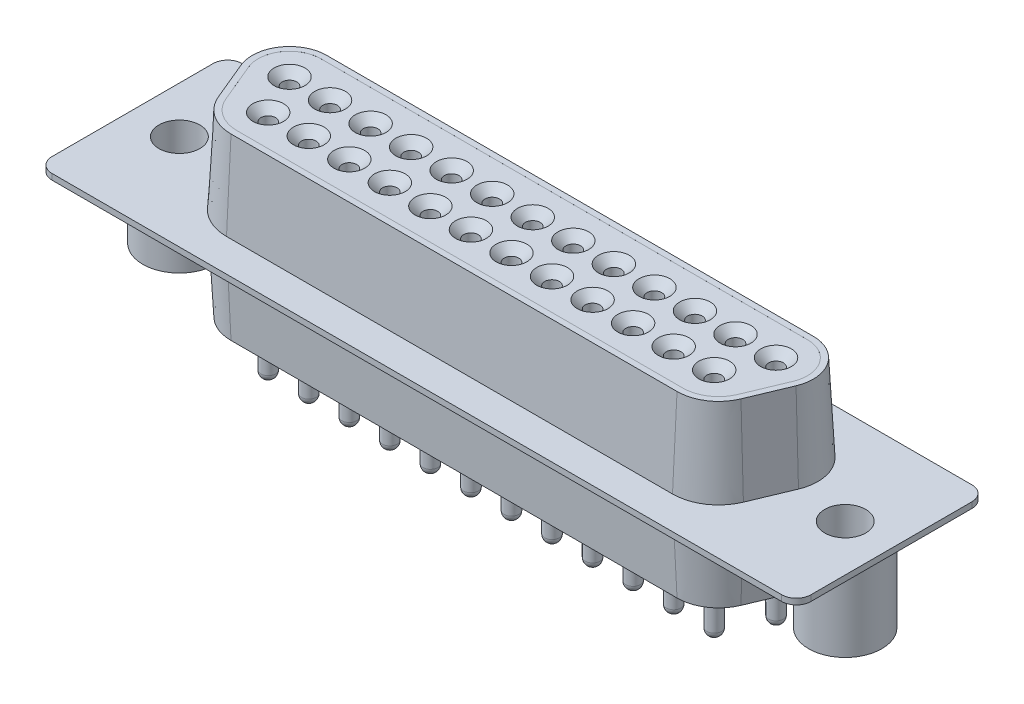
SolidWorks part; units mm, degrees
ref_plane "Front" through (0, 0, 0) normal (0, 0, 1) x (1, 0, 0)
ref_plane "Top" through (0, 0, 0) normal (0, 1, 0) x (1, 0, 0)
ref_plane "Right" through (0, 0, 0) normal (1, 0, 0) x (0, 0, -1)
sketch "Sketch1" plane through (0, 0, 0) normal (0, 1, 0) x (1, 0, 0)
  line L0 (0, 2.54) -> (33.24, 2.54)
  line L1 (1.385, -5.38) -> (31.855, -5.38)
  line L2 (34.476, -3.6337) -> (35.5841, -0.9782)
  line L3 (16.62, 2.54) -> (16.62, -5.38) construction
  line L4 (-1.236, -3.6337) -> (-2.3441, -0.9782)
  arc A0 (31.855, -5.38) -> (34.476, -3.6337) centre (31.855, -2.54) ccw
  arc A1 (35.5841, -0.9782) -> (33.24, 2.54) centre (33.24, 0) ccw
  arc A2 (-2.3441, -0.9782) -> (0, 2.54) centre (0, 0) cw
  arc A3 (1.385, -5.38) -> (-1.236, -3.6337) centre (1.385, -2.54) cw
  dimension "D3" = 2.84
  dimension "D6" = 2.54
  dimension "D1" = 33.24
  dimension "D2" = 30.47
  dimension "D4" = 2.54
  dimension "D5" = 7.92
extrude "Base-Extrude" add sketch "Sketch1" against normal blind 5.91 draft 3 draft outward yes
sketch "Sketch2" plane through (0, -5.91, 0) normal (0, -1, 0) x (1, 0, 0)
  line L0 (16.62, -2.8497) -> (16.62, -5.08) construction
  line L1 (41.545, 7.92) -> (-8.305, 7.92)
  line L2 (42.545, 6.92) -> (42.545, -4.08)
  line L3 (41.545, -5.08) -> (-8.305, -5.08)
  line L4 (-9.305, 6.92) -> (-9.305, -4.08)
  line L5 (33.24, -2.8497) -> (0, -2.8497) construction
  line L6 (16.62, -2.8497) -> (16.62, 5.6897) construction
  line L7 (1.385, 5.6897) -> (31.855, 5.6897) construction
  line L8 (16.62, 1.42) -> (42.545, 1.42) construction
  arc A0 (42.545, 6.92) -> (41.545, 7.92) centre (41.545, 6.92) ccw
  arc A1 (41.545, -5.08) -> (42.545, -4.08) centre (41.545, -4.08) ccw
  arc A2 (-9.305, 6.92) -> (-8.305, 7.92) centre (-8.305, 6.92) cw
  arc A3 (-9.305, -4.08) -> (-8.305, -5.08) centre (-8.305, -4.08) ccw
  point P15 (42.545, 7.92)
  point P18 (42.545, -5.08)
  point P23 (-9.305, -5.08)
  dimension "D3" = 1
  dimension "D1" = 51.85
  dimension "D2" = 13
extrude "Boss-Extrude1" add sketch "Sketch2" along normal blind 0.2
sketch "Sketch3" plane through (0, 0, 0) normal (0, 1, 0) x (-1, 0, 0)
  line L8 (-33.24, -2.14) -> (0, -2.14)
  line L9 (1.9749, 0.8241) -> (0.8668, 3.4797)
  line L10 (-1.385, 4.98) -> (-31.855, 4.98)
  line L11 (-34.1068, 3.4797) -> (-35.2149, 0.8241)
  line L12 (-33.24, -2.14) -> (0, -2.14)
  line L13 (1.9749, 0.8241) -> (0.8668, 3.4797)
  line L14 (-1.385, 4.98) -> (-31.855, 4.98)
  line L15 (-34.1068, 3.4797) -> (-35.2149, 0.8241)
  arc A8 (0, -2.14) -> (1.9749, 0.8241) centre (0, 0) ccw
  arc A9 (0.8668, 3.4797) -> (-1.385, 4.98) centre (-1.385, 2.54) ccw
  arc A10 (-31.855, 4.98) -> (-34.1068, 3.4797) centre (-31.855, 2.54) ccw
  arc A11 (-35.2149, 0.8241) -> (-33.24, -2.14) centre (-33.24, 0) ccw
  arc A12 (0, -2.14) -> (1.9749, 0.8241) centre (0, 0) ccw
  arc A13 (0.8668, 3.4797) -> (-1.385, 4.98) centre (-1.385, 2.54) ccw
  arc A14 (-31.855, 4.98) -> (-34.1068, 3.4797) centre (-31.855, 2.54) ccw
  arc A15 (-35.2149, 0.8241) -> (-33.24, -2.14) centre (-33.24, 0) ccw
  dimension "D1" = 0.4
extrude "Cut-Extrude1" cut sketch "Sketch3" against normal blind 0.001
mirror "Boss-Mirror1" about plane through (41.545, -6.11, 6.92) normal (0, -1, 0) of bodies 103
sketch "Sketch4" plane through (0, -0.001, 0) normal (0, 1, 0) x (-1, 0, 0)
  circle A0 centre (0, 0) radius 0.5
  dimension "D1" = 1
extrude "Cut-Extrude5" cut sketch "Sketch4" against normal blind 6
sketch "Sketch5" plane through (0, -12.219, 0) normal (0, -1, 0) x (1, 0, 0)
  circle A1 centre (0, 0) radius 0.5
  circle A2 centre (0, 0) radius 0.5 construction
extrude "Boss-Extrude5" add sketch "Sketch5" along normal blind 3
dome "Dome3" faces to dome 1 distance 0.5 reverse direction no elliptical dome no face at (0, -15.219, -0.5) parameters "D1"=0.5
chamfer "Chamfer1" distance 0.55 angle 45 1 edges at (0, -0.001, 0.5)
pattern_linear "LPattern1" count 13 spacing 2.77 along (1, 0, 0) of "Cut-Extrude5", "Boss-Extrude5", "Dome3", "Chamfer1"
sketch "Sketch6" plane through (0, -0.001, 0) normal (0, 1, 0) x (-1, 0, 0)
  line L0 (0, 0) -> (-2.77, 0) construction
  line L1 (-1.385, 0) -> (-1.385, 2.84) construction
  circle A0 centre (-1.385, 2.84) radius 0.5
  circle A3 centre (0, 0) radius 0.5 construction
  circle A4 centre (-2.77, 0) radius 0.5 construction
  dimension "D1" = 2.84
extrude "Cut-Extrude8" cut sketch "Sketch6" against normal blind 6
sketch "Sketch7" plane through (0, -12.219, 0) normal (0, -1, 0) x (1, 0, 0)
  circle A1 centre (1.385, 2.84) radius 0.5
extrude "Boss-Extrude6" add sketch "Sketch7" along normal blind 3
dome "Dome4" faces to dome 1 distance 0.5 reverse direction no elliptical dome no face at (1.385, -15.219, 2.34) parameters "D1"=0.5
chamfer "Chamfer3" distance 0.55 angle 45 1 edges at (1.385, -0.001, 3.34)
pattern_linear "LPattern3" count 12 spacing 2.77 along (1, 0, 0) of "Dome4", "Boss-Extrude6", "Cut-Extrude8", "Chamfer3"
ref_plane "Plane1" through (16.62, 0, 0) normal (1, 0, 0) x (0, 0, -1)
sketch "Sketch8" plane through (0, -6.31, 0) normal (0, 1, 0) x (-1, 0, 0)
  line L0 (-42.545, -4.08) -> (-42.545, 6.92) construction
  line L1 (8.305, -5.08) -> (-41.545, -5.08) construction
  circle A0 centre (-39.365, 1.4) radius 2.5
  dimension "D1" = 5
  dimension "D2" = 3.18
  dimension "D3" = 6.48
extrude "Boss-Extrude4" add sketch "Sketch8" against normal blind 5.9
sketch "Sketch9" plane through (0, -12.21, 0) normal (0, -1, 0) x (1, 0, 0)
  circle A0 centre (39.365, 1.4) radius 1.4
  circle A1 centre (39.365, 1.4) radius 2.5 construction
  dimension "D1" = 2.8
extrude "Cut-Extrude4" cut sketch "Sketch9" against normal through all
mirror "Mirror1" about plane through (16.62, 0, 0) normal (1, 0, 0) of "Boss-Extrude4", "Cut-Extrude4"
